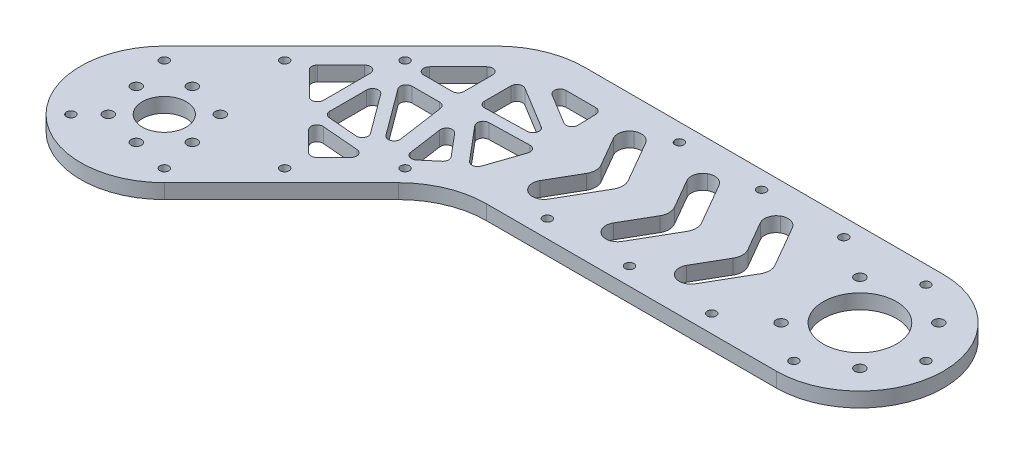
SolidWorks part; units mm, degrees
material "AISI 304"
ref_plane "前视基准面" through (0, 0, 0) normal (0, 0, 1) x (1, 0, 0)
ref_plane "上视基准面" through (0, 0, 0) normal (0, 1, 0) x (1, 0, 0)
ref_plane "右视基准面" through (0, 0, 0) normal (1, 0, 0) x (0, 0, -1)
sketch "草图1" plane through (0, 0, 0) normal (0, 1, 0) x (1, 0, 0)
  line L0 (-20.1525, 20.1525) -> (45.1949, 85.5)
  line L1 (20.1525, -20.1525) -> (68.8051, 28.5)
  line L2 (68.8051, 28.5) -> (180, 28.5)
  line L3 (45.1949, 85.5) -> (180, 85.5)
  line L4 (20.1525, -20.1525) -> (137.6118, -20.1525) construction
  circle A0 centre (0, 0) radius 28.5
  circle A1 centre (180, 57) radius 28.5
  dimension "D1" = 57
  dimension "D3" = 57
  dimension "D2" = 57
  dimension "D4" = 57
  dimension "D5" = 45
  dimension "D6" = 180
extrude "凸台-拉伸1" add sketch "草图1" along normal blind 5 contours A1 L3 L0 A0 L1 L2 | A0 | A1 region at (80.8159, 0, -50.6724) region at (0, 0, 0) region at (180, 0, -57)
fillet "圆角1" radius 30 1 edges at (68.8051, 2.5, -28.5)
fillet "圆角2" radius 30 1 edges at (45.1949, 2.5, -85.5)
sketch "草图2" plane through (0, 5, 0) normal (0, 1, 0) x (1, 0, 0)
  line L0 (180, 57) -> (-10.2315, 57) construction
  line L1 (150, 57) -> (138.453, 77)
  line L2 (138.453, 77) -> (131.5248, 73)
  line L3 (131.5248, 73) -> (140.7624, 57)
  line L4 (131.5248, 41) -> (140.7624, 57)
  line L5 (150, 57) -> (138.453, 37)
  line L6 (138.453, 37) -> (131.5248, 41)
  line L7 (106.5248, 41) -> (115.7624, 57)
  line L8 (106.5248, 73) -> (115.7624, 57)
  line L9 (113.453, 77) -> (106.5248, 73)
  line L10 (125, 57) -> (113.453, 77)
  line L11 (125, 57) -> (113.453, 37)
  line L12 (113.453, 37) -> (106.5248, 41)
  line L13 (81.5248, 41) -> (90.7624, 57)
  line L14 (81.5248, 73) -> (90.7624, 57)
  line L15 (88.453, 77) -> (81.5248, 73)
  line L16 (100, 57) -> (88.453, 77)
  line L17 (100, 57) -> (88.453, 37)
  line L18 (88.453, 37) -> (81.5248, 41)
  dimension "D1" = 8
  dimension "D2" = 20
  dimension "D3" = 30
  dimension "D4" = 60
  dimension "D5" = 3
extrude "切除-拉伸1" cut sketch "草图2" against normal blind 17
fillet "圆角3" radius 5 6 edges at (140.7624, 2.5, -57) (115.7624, 2.5, -57) (90.7624, 2.5, -57) (100, 2.5, -57) (125, 2.5, -57) (150, 2.5, -57)
fillet "圆角4" radius 4 12 edges at (88.453, 2.5, -37) (81.5248, 2.5, -41) (81.5248, 2.5, -73) (106.5248, 2.5, -73) (88.453, 2.5, -77) (113.453, 2.5, -77) (113.453, 2.5, -37) (106.5248, 2.5, -41) (131.5248, 2.5, -41) (138.453, 2.5, -37) (131.5248, 2.5, -73) (138.453, 2.5, -77)
sketch "草图3" plane through (0, 0, 0) normal (0, -1, 0) x (1, 0, 0)
  line L0 (180, -57) -> (216.2615, -57) construction
  line L1 (180, -57) -> (193.435, -43.565) construction
  circle A0 centre (180, -57) radius 19 construction
  circle A7 centre (193.435, -43.565) radius 1.75
  circle A8 centre (193.435, -70.435) radius 1.75
  circle A9 centre (166.565, -70.435) radius 1.75
  circle A10 centre (166.565, -43.565) radius 1.75
  point P15 (180, -57)
  point P18 (180, -57)
  dimension "D1" = 38
  dimension "D2" = 45
  dimension "D3" = 3.5
  dimension "D4" = 4
extrude "切除-拉伸2" cut sketch "草图3" against normal blind 22
sketch "草图4" plane through (0, 0, 0) normal (0, -1, 0) x (1, 0, 0)
  line L0 (0, 0) -> (-20.1525, 20.1525) construction
  circle A0 centre (0, 0) radius 13.5 construction
  circle A1 centre (3.4941, 13.04) radius 1.75
  circle A2 centre (-9.5459, 9.5459) radius 1.75
  circle A3 centre (13.04, 3.4941) radius 1.75
  circle A4 centre (9.5459, -9.5459) radius 1.75
  circle A5 centre (-3.4941, -13.04) radius 1.75
  circle A6 centre (-13.04, -3.4941) radius 1.75
  point P20 (0, 0)
  dimension "D1" = 27
  dimension "D2" = 3.5
  dimension "D3" = 6
extrude "切除-拉伸3" cut sketch "草图4" against normal blind 9
sketch "草图5" plane through (0, 5, 0) normal (0, 1, 0) x (1, 0, 0)
  line L0 (0, 0) -> (65.1893, 65.1893) construction
  line L1 (-20.1525, 20.1525) -> (36.4081, 76.7132) construction
  line L2 (47.7297, 30.052) -> (30.052, 47.7297)
  line L3 (30.052, 47.7297) -> (28.2843, 28.2843)
  line L4 (24.7487, 50.2046) -> (12.0208, 37.4767)
  line L5 (12.0208, 37.4767) -> (22.6274, 26.8701)
  line L6 (22.6274, 26.8701) -> (24.7487, 50.2046)
  line L7 (47.7297, 30.052) -> (28.2843, 28.2843)
  line L8 (37.4767, 12.0208) -> (26.8701, 22.6274)
  line L9 (50.2046, 24.7487) -> (37.4767, 12.0208)
  line L10 (26.8701, 22.6274) -> (50.2046, 24.7487)
  point P12 (38.8909, 38.8909)
  dimension "D1" = 15
  dimension "D2" = 18
  dimension "D3" = 25
  dimension "D4" = 3
  dimension "D5" = 35
  dimension "D6" = 20
sketch "草图7" plane through (0, 5, 0) normal (0, 1, 0) x (1, 0, 0)
  line L0 (180, 57) -> (5.0176, 57) construction
  line L4 (37.3024, 11.8794) -> (47.5413, 22.1184)
  line L8 (89.9889, 57) -> (89.9889, 67.6591) construction
  line L9 (73.4605, 75.5061) -> (73.7578, 63.626)
  line L10 (73.7578, 63.626) -> (54.2263, 75.5061)
  line L11 (54.2263, 75.5061) -> (73.4605, 75.5061)
  line L12 (44.295, 72.4023) -> (27.7117, 55.819)
  line L13 (27.7117, 55.819) -> (44.295, 55.819)
  line L14 (44.295, 55.819) -> (44.295, 72.4023)
  line L15 (50.6369, 71.0152) -> (50.6369, 56.4235)
  line L16 (50.6369, 56.4235) -> (73.6786, 57)
  line L17 (73.6786, 57) -> (50.6369, 71.0152)
  line L18 (53.5277, 52.7613) -> (74.2599, 53.28)
  line L19 (74.2599, 53.28) -> (68.128, 35.4384)
  line L20 (68.128, 35.4384) -> (53.5277, 52.7613)
  line L21 (53.6788, 27.1882) -> (62.7017, 34.7929)
  line L22 (62.7017, 34.7929) -> (50.531, 49.2331)
  line L23 (50.531, 49.2331) -> (53.6788, 27.1882)
  line L24 (45.0473, 50.5224) -> (29.9222, 50.5224)
  line L25 (29.9222, 50.5224) -> (48.6672, 25.1716)
  line L26 (48.6672, 25.1716) -> (45.0473, 50.5224)
  line L27 (22.9587, 52.0768) -> (10.1382, 39.2563)
  line L28 (10.1382, 39.2563) -> (22.9587, 26.4359)
  line L29 (22.9587, 26.4359) -> (22.9587, 52.0768)
  line L30 (27.2619, 47.7479) -> (43.3792, 25.9508)
  line L31 (43.3792, 25.9508) -> (27.2619, 27.2619)
  line L32 (0, 0) -> (65.1893, 65.1893) construction
  line L33 (27.2619, 27.2619) -> (27.2619, 47.7479)
  line L34 (47.5413, 22.1184) -> (25.2502, 23.9316)
  line L35 (25.2502, 23.9316) -> (37.3024, 11.8794)
  line L36 (57.6213, 85.5) -> (180, 85.5) construction
  line L37 (-20.1525, 20.1525) -> (36.4081, 76.7132) construction
  line L38 (20.1525, -20.1525) -> (60.0183, 19.7132) construction
  arc A0 (89.319, 54.5) -> (89.319, 59.5) centre (84.9889, 57) ccw construction
extrude "切除-拉伸6" cut sketch "草图7" against normal blind 10
fillet "圆角7" radius 2 18 edges at (29.9222, 2.5, -50.5224) (48.6672, 2.5, -25.1716) (45.0473, 2.5, -50.5224) (53.6788, 2.5, -27.1882) (62.7017, 2.5, -34.7929) (50.531, 2.5, -49.2331) (68.128, 2.5, -35.4384) (53.5277, 2.5, -52.7613) (74.2599, 2.5, -53.28) (73.7578, 2.5, -63.626) (54.2263, 2.5, -75.5061) (73.4605, 2.5, -75.5061) (50.6369, 2.5, -56.4235) (73.6786, 2.5, -57) (50.6369, 2.5, -71.0152) (44.295, 2.5, -55.819) (27.7117, 2.5, -55.819) (44.295, 2.5, -72.4023)
fillet "圆角8" radius 2 9 edges at (37.3024, 2.5, -11.8794) (25.2502, 2.5, -23.9316) (47.5413, 2.5, -22.1184) (43.3792, 2.5, -25.9508) (27.2619, 2.5, -27.2619) (27.2619, 2.5, -47.7479) (22.9587, 2.5, -26.4359) (10.1382, 2.5, -39.2563) (22.9587, 2.5, -52.0768)
sketch "草图8" plane through (0, 5, 0) normal (0, 1, 0) x (1, 0, 0)
  line L0 (0, 0) -> (-15.9099, -15.9099) construction
  line L1 (-20.1525, 20.1525) -> (20.1525, -20.1525) construction
  line L2 (-15.9099, 15.9099) -> (45.5568, 77.3766) construction
  line L3 (-20.1525, 20.1525) -> (36.4081, 76.7132) construction
  line L4 (15.9099, -15.9099) -> (54.5464, 22.7266) construction
  line L5 (20.1525, -20.1525) -> (60.0183, 19.7132) construction
  line L6 (180, 79.5) -> (59.1595, 79.5) construction
  line L7 (180, 34.5) -> (75.7291, 34.5) construction
  circle A0 centre (0, 0) radius 22.5 construction
  circle A1 centre (-15.9099, -15.9099) radius 1.5
  circle A2 centre (-15.9099, 15.9099) radius 1.5
  circle A3 centre (15.9099, -15.9099) radius 1.5
  circle A4 centre (4.5962, 36.416) radius 1.5
  circle A5 centre (25.1023, 56.9221) radius 1.5
  circle A7 centre (36.416, 4.5962) radius 1.5
  circle A8 centre (56.9221, 25.1023) radius 1.5
  circle A9 centre (180, 57) radius 22.5 construction
  circle A10 centre (180, 79.5) radius 1.5
  circle A11 centre (180, 34.5) radius 1.5
  circle A12 centre (152, 79.5) radius 1.5
  circle A13 centre (124, 79.5) radius 1.5
  circle A14 centre (96, 79.5) radius 1.5
  circle A16 centre (152, 34.5) radius 1.5
  circle A17 centre (124, 34.5) radius 1.5
  circle A18 centre (96, 34.5) radius 1.5
  circle A19 centre (202.5, 57) radius 1.5
  dimension "D1" = 45
  dimension "D2" = 3
  dimension "D3" = 3
  dimension "D4" = 3
  dimension "D7" = 45
  dimension "D8" = 3
  dimension "D9" = 3
  dimension "D12" = 3
  dimension "D5" = 3
  dimension "D6" = 3
  dimension "D10" = 4
  dimension "D11" = 4
extrude "切除-拉伸7" cut sketch "草图8" against normal blind 10
sketch "草图9" plane through (0, 5, 0) normal (0, 1, 0) x (1, 0, 0)
  line L0 (46.1408, 83.2164) -> (69.751, 26.2164) construction
  arc A0 (57.6213, 85.5) -> (36.4081, 76.7132) centre (57.6213, 55.5) ccw construction
  arc A1 (81.2315, 28.5) -> (60.0183, 19.7132) centre (81.2315, -1.5) ccw construction
sketch "草图10" plane through (0, 5, 0) normal (0, 1, 0) x (1, 0, 0)
  circle A0 centre (0, 0) radius 7.5
  circle A1 centre (180, 57) radius 12.5
  dimension "D1" = 15
  dimension "D2" = 25
extrude "切除-拉伸8" cut sketch "草图10" against normal blind 10
